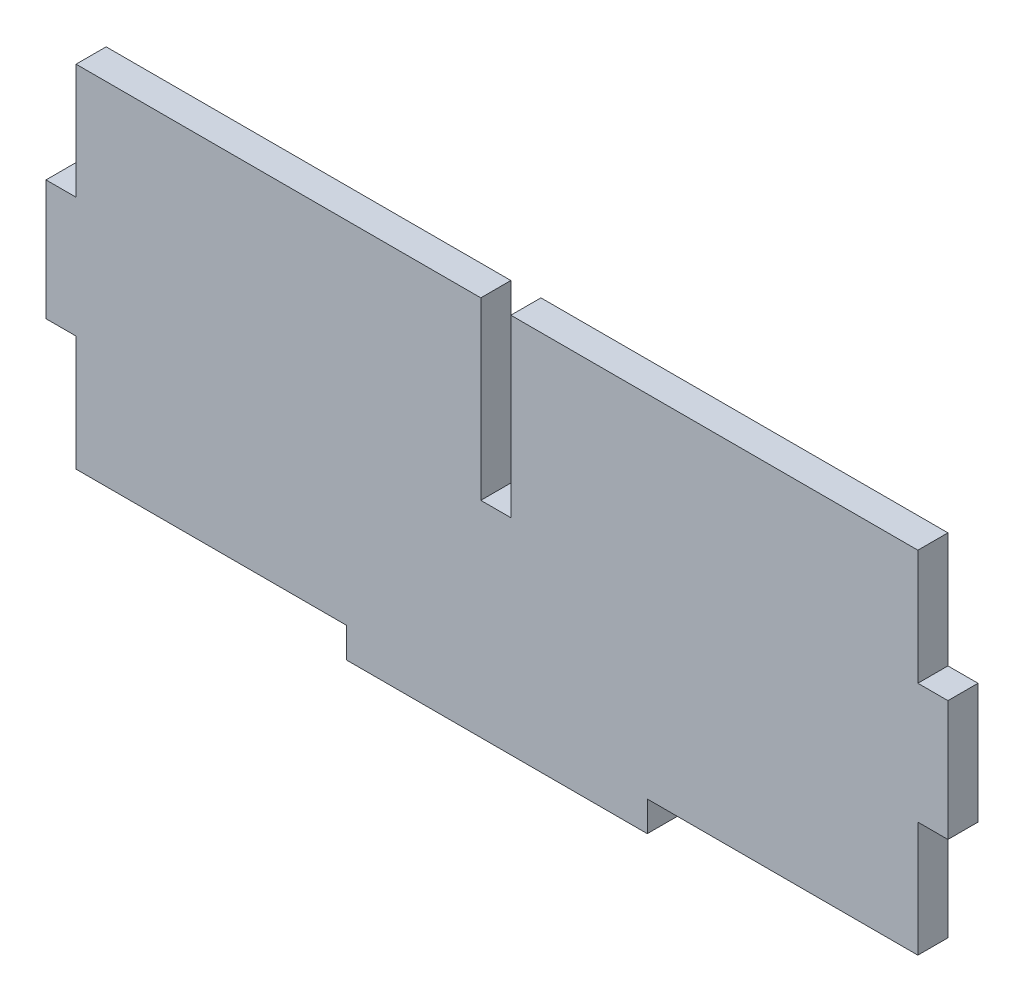
SolidWorks part; units mm, degrees
ref_plane "Front Plane" through (0, 0, 0) normal (0, 0, 1) x (1, 0, 0)
ref_plane "Top Plane" through (0, 0, 0) normal (0, 1, 0) x (1, 0, 0)
ref_plane "Right Plane" through (0, 0, 0) normal (1, 0, 0) x (0, 0, -1)
sketch "Sketch1" plane through (0, 0, 0) normal (0, 0, 1) x (1, 0, 0)
  line L0 (-42, -19) -> (-42, -4.5)
  line L1 (-45, -19) -> (45, -19)
  line L2 (-45, -19) -> (-45, 19)
  line L3 (-45, 19) -> (45, 19)
  line L4 (45, -19) -> (45, 19)
  line L5 (-45, -19) -> (45, 19) construction
  line L6 (-45, 19) -> (45, -19) construction
  line L7 (-42, -4.5) -> (-45, -4.5)
  line L8 (-45, 7.5) -> (-42, 7.5)
  line L9 (45, -4.5) -> (42, -4.5)
  line L10 (42, -4.5) -> (42, -19)
  line L11 (-42, 7.5) -> (-42, 19)
  line L12 (45, 7.5) -> (42, 7.5)
  line L13 (42, 7.5) -> (42, 19)
  line L14 (-45, -16) -> (-15, -16)
  line L15 (-15, -16) -> (-15, -19)
  line L16 (45, -16) -> (15, -16)
  line L17 (15, -16) -> (15, -19)
  line L19 (-1.613, 1.5) -> (1.387, 1.5)
  line L20 (-1.613, 1.5) -> (-1.613, 19)
  line L21 (-1.613, 19) -> (1.387, 19)
  line L22 (1.387, 1.5) -> (1.387, 19)
  line L23 (-1.613, 1.5) -> (1.387, 19) construction
  line L24 (-1.613, 19) -> (1.387, 1.5) construction
  point P0 (0, 0)
  point P23 (-0.113, 10.25)
  dimension "D1" = 90
  dimension "D2" = 38
  dimension "D3" = 11.5
  dimension "D4" = 30
  dimension "D5" = 3
  dimension "D6" = 12
  dimension "D7" = 30
  dimension "D8" = 3
  dimension "D9" = 17.5
  dimension "D10" = 3
  dimension "D11" = 12
extrude "Boss-Extrude1" add sketch "Sketch1" along normal blind 3 contours L3 L2 L1 L10 L9 L4 region at (0.0019, 0.7886, 0)
